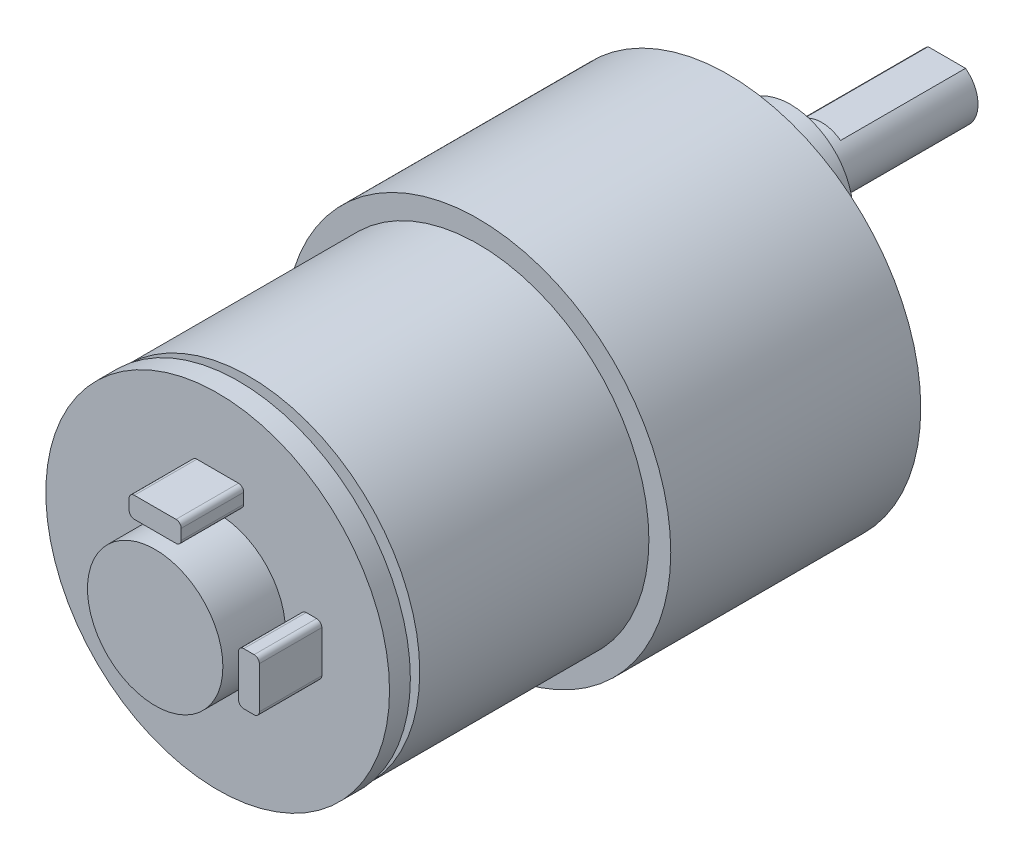
SolidWorks part; units mm, degrees
ref_plane "前视基准面" through (0, 0, 0) normal (0, 0, 1) x (1, 0, 0)
ref_plane "上视基准面" through (0, 0, 0) normal (0, 1, 0) x (1, 0, 0)
ref_plane "右视基准面" through (0, 0, 0) normal (1, 0, 0) x (0, 0, -1)
sketch "草图1" plane through (0, 0, 0) normal (0, 0, 1) x (1, 0, 0)
  circle A0 centre (0, 0) radius 18.5
  circle A1 centre (-15.5, 0) radius 1.5
  circle A2 centre (-7.75, 13.4234) radius 1.5
  circle A3 centre (7.75, 13.4234) radius 1.5
  circle A4 centre (15.5, 0) radius 1.5
  circle A5 centre (7.75, -13.4234) radius 1.5
  circle A6 centre (-7.75, -13.4234) radius 1.5
  point P17 (0, 0)
  dimension "D1" = 37
  dimension "D2" = 3
  dimension "D3" = 15.5
  dimension "D4" = 6
extrude "凸台-拉伸1" add sketch "草图1" along normal blind 24 contours A0
extrude "切除-拉伸1" cut sketch "草图1<3>" along normal offset from surface (20 mm away) 4 contours A1 | A2 | A6 | A3 | A4 | A5 region at (-15.5, 0, 0) up to face at (18.5, 0, 24)
sketch "草图1<3>" plane through (0, 0, 0) normal (0, 0, 1) x (1, 0, 0) same geometry as "草图1"
sketch "草图3" plane through (0, 0, 24) normal (0, 0, 1) x (1, 0, 0)
  circle A0 centre (0, 0) radius 16.4
  dimension "D1" = 32.8
extrude "凸台-拉伸3" add sketch "草图3" along normal blind 22
sketch "草图4" plane through (0, 0, 0) normal (0, 0, -1) x (-1, 0, 0)
  circle A0 centre (0, 7) radius 6
  dimension "D2" = 12
  dimension "D1" = 7
extrude "凸台-拉伸4" add sketch "草图4" along normal blind 6
sketch "草图5" plane through (0, 0, -6) normal (0, 0, -1) x (-1, 0, 0)
  circle A0 centre (0, 7) radius 3
  dimension "D1" = 6
extrude "凸台-拉伸5" add sketch "草图5" along normal blind 3
sketch "草图6" plane through (0, 0, -9) normal (0, 0, -1) x (-1, 0, 0)
  line L0 (-1.8, 9.4) -> (1.8, 9.4)
  circle A1 centre (0, 7) radius 3
  arc A2 (-1.8, 9.4) -> (1.8, 9.4) centre (0, 7) ccw
  dimension "D2" = 2.4
  dimension "D1" = 0
extrude "凸台-拉伸6" add sketch "草图6" along normal blind 12
sketch "草图7" plane through (0, 0, 46) normal (0, 0, 1) x (1, 0, 0)
  circle A0 centre (0, 0) radius 15
  dimension "D1" = 30
extrude "凸台-拉伸7" add sketch "草图7" along normal blind 1
sketch "草图8" plane through (0, 0, 47) normal (0, 0, 1) x (1, 0, 0)
  circle A0 centre (0, 0) radius 16.5
  dimension "D1" = 33
extrude "凸台-拉伸8" add sketch "草图8" along normal blind 2
sketch "草图9" plane through (0, 0, 49) normal (0, 0, 1) x (1, 0, 0)
  line L1 (-2, 10) -> (2, 10)
  line L2 (-2.5, 9.5) -> (-2.5, 8.5)
  line L3 (-2, 8) -> (2, 8)
  line L4 (2.5, 9.5) -> (2.5, 8.5)
  line L5 (8.5, 2.5) -> (9.5, 2.5)
  line L6 (8, 2) -> (8, -2)
  line L7 (8.5, -2.5) -> (9.5, -2.5)
  line L8 (10, 2) -> (10, -2)
  circle A0 centre (0, 0) radius 6.5
  arc A1 (9.5, -2.5) -> (10, -2) centre (9.5, -2) ccw
  arc A2 (8, -2) -> (8.5, -2.5) centre (8.5, -2) ccw
  arc A3 (8.5, 2.5) -> (8, 2) centre (8.5, 2) ccw
  arc A4 (2, 8) -> (2.5, 8.5) centre (2, 8.5) ccw
  arc A5 (2, 10) -> (2.5, 9.5) centre (2, 9.5) cw
  arc A6 (-2.5, 8.5) -> (-2, 8) centre (-2, 8.5) ccw
  arc A7 (-2, 10) -> (-2.5, 9.5) centre (-2, 9.5) ccw
  arc A8 (9.5, 2.5) -> (10, 2) centre (9.5, 2) cw
  point P11 (0, 0)
  point P12 (0, 8)
  point P13 (0, 0)
  point P14 (8, 0)
  point P17 (10, -2.5)
  point P22 (8, 2.5)
  point P25 (2.5, 8)
  point P28 (2.5, 10)
  point P33 (-2.5, 10)
  point P36 (10, 2.5)
  dimension "D1" = 13
  dimension "D8" = 0.5
  dimension "D9" = 0.5
  dimension "D2" = 8
  dimension "D3" = 8
  dimension "D4" = 2
  dimension "D5" = 2
  dimension "D6" = 5
  dimension "D7" = 5
extrude "凸台-拉伸9" add sketch "草图9" along normal blind 6
